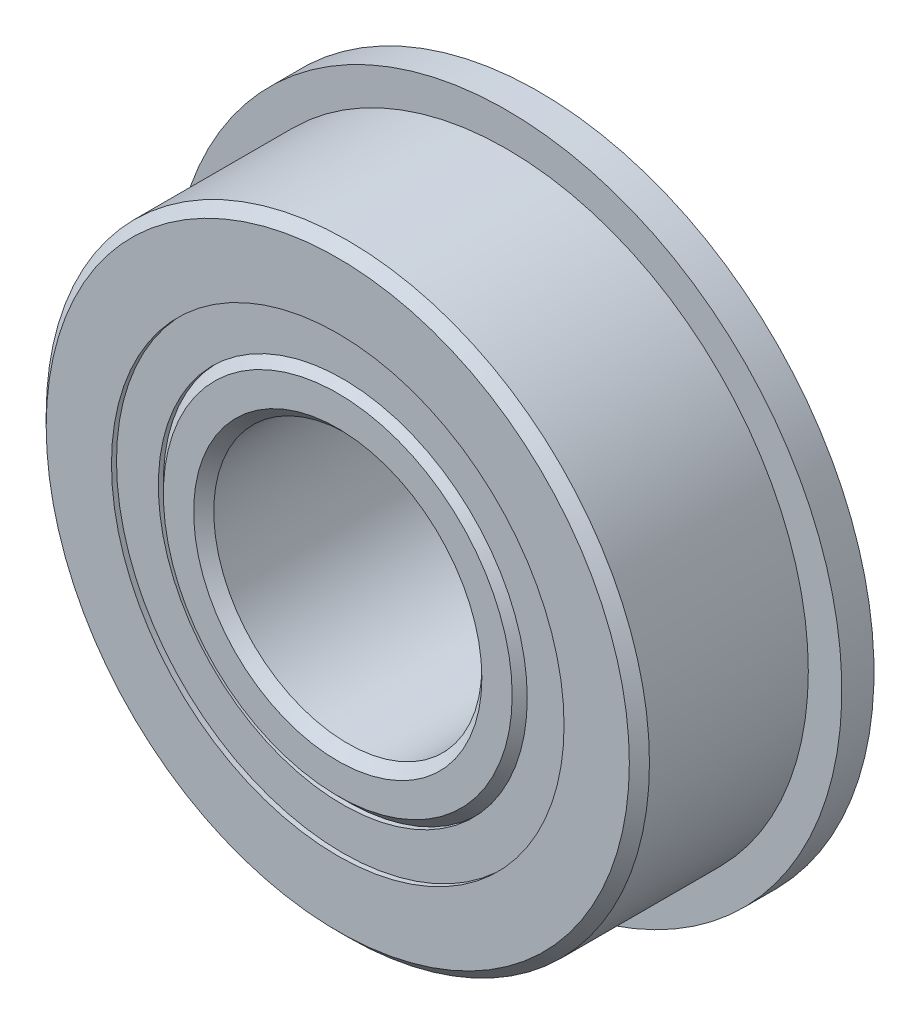
SolidWorks part; units mm, degrees
ref_plane "Front Plane" through (0, 0, 0) normal (0, 0, 1) x (1, 0, 0)
ref_plane "Top Plane" through (0, 0, 0) normal (0, 1, 0) x (1, 0, 0)
ref_plane "Right Plane" through (0, 0, 0) normal (1, 0, 0) x (0, 0, -1)
sketch "Sketch1" plane through (0, 0, 0) normal (1, 0, 0) x (0, 0, -1)
  line L0 (-4.7625, 0) -> (4.7625, 0) construction
  line L1 (0, 14.2875) -> (0, -14.2875) construction
  line L2 (4.2863, 14.2875) -> (-4.2862, 14.2875)
  line L3 (-4.2862, 14.2875) -> (-4.7625, 13.8112)
  line L4 (-4.7625, 13.8112) -> (-4.7625, 10.7188)
  line L5 (-4.7625, 10.7188) -> (-2.3474, 10.7188)
  line L6 (4.7625, 10.7188) -> (2.3474, 10.7188)
  line L7 (4.7625, 13.8112) -> (4.7625, 10.7188)
  line L8 (4.2863, 14.2875) -> (4.7625, 13.8112)
  line L9 (0, 14.2875) -> (0, 10.3187) construction
  line L10 (0, 10.3187) -> (0, 6.35) construction
  line L11 (4.7625, 8.7376) -> (4.7625, -8.7376) construction
  line L12 (-4.7625, 6.35) -> (4.7625, 6.35) construction
  line L13 (0, 7.9375) -> (0, 6.35) construction
  line L14 (0, 12.7) -> (0, 14.2875) construction
  line L15 (4.7625, 8.7376) -> (0, 8.7376) construction
  circle A1 centre (0, 10.3187) radius 2.3813 construction
  arc A2 (-2.3474, 10.7188) -> (2.3474, 10.7188) centre (0, 10.3187) cw
  point P14 (0, 6.35)
  point P22 (0, 7.9375)
  point P23 (0, 12.7)
  dimension "D3" = 4.7625
  dimension "Width" = 9.525
  dimension "OD" = 28.575
  dimension "D1" = 45
  dimension "D2" = 0.4763
  dimension "D4" = 17.4752
  dimension "D5" = 3.9624
  dimension "D6" = 1.9812
revolve "Revolve1" add sketch "Sketch1" angle 360 about L0
sketch "Sketch3" plane through (0, 0, 0) normal (1, 0, 0) x (0, 0, -1)
  line L1 (-4.7625, 13.8112) -> (-4.7625, 10.7188) construction
  line L2 (-4.2862, 14.2875) -> (-4.7625, 13.8112) construction
  line L3 (-4.7625, 9.9187) -> (-4.7625, 6.8262) construction
  line L4 (-4.7625, 6.8262) -> (-4.7625, 8.2614)
  line L5 (-4.7625, 6.8262) -> (-4.2862, 6.35)
  line L6 (-4.2862, 6.35) -> (5.8865, 6.35)
  line L7 (-4.7625, 13.8112) -> (-4.7625, -13.8112) construction
  line L8 (5.8865, 6.35) -> (6.3627, 6.8262)
  line L9 (0, 0) -> (6.3627, 0) construction
  line L13 (4.2863, 14.2875) -> (4.7625, 13.8112) construction
  line L14 (-4.7625, 8.2614) -> (-4.2862, 8.7376)
  line L15 (-4.2862, 8.7376) -> (-1.7805, 8.7376)
  line L16 (1.7805, 8.7376) -> (5.8865, 8.7376)
  line L17 (5.8865, 8.7376) -> (6.3627, 8.2614)
  line L18 (6.3627, 8.2614) -> (6.3627, 6.8262)
  circle A0 centre (0, 10.3187) radius 2.3812 construction
  arc A1 (-1.7805, 8.7376) -> (1.7805, 8.7376) centre (0, 10.3187) ccw
  dimension "D1" = 45
  dimension "Ring Wd" = 11.1252
  dimension "Inner Ring OD" = 17.4752
revolve "Revolve3" add sketch "Sketch3" angle 360 about L0
sketch "Sketch6" plane through (0, 0, 0) normal (1, 0, 0) x (0, 0, -1)
  line L1 (4.7625, 10.7188) -> (3.2385, 10.7188)
  line L2 (4.7625, 10.7188) -> (4.7625, 15.875)
  line L3 (4.7625, 15.875) -> (3.2385, 15.875)
  line L4 (3.2385, 10.7188) -> (3.2385, 15.875)
  line L5 (4.7625, 0) -> (-4.7625, 0) construction
  dimension "Flange OD" = 31.75
  dimension "Flange Thickness" = 1.524
revolve "Revolve6" add sketch "Sketch6" angle 360 about L5
sketch "Sketch4" plane through (0, 0, 0) normal (1, 0, 0) x (0, 0, -1)
  line L0 (-2.3813, 10.3187) -> (2.3813, 10.3187)
  circle A0 centre (0, 10.3187) radius 2.3812 construction
  arc A1 (2.3813, 10.3187) -> (-2.3813, 10.3187) centre (0, 10.3187) ccw
revolve "Revolve4" add sketch "Sketch4" angle 360 about L0
ref_axis "Axis1" through (0, 0, -4.7625) along (0, 0, 1)
pattern_circular "CirPattern1" count 12 every 30 about axis through (0, 0, -4.7625) along (0, 0, 1) of bodies 104
sketch "Sketch5" plane through (0, 0, 0) normal (1, 0, 0) x (0, 0, -1)
  line L0 (-4.7625, 10.7188) -> (-2.3474, 10.7188) construction
  line L1 (-4.5244, 10.7188) -> (-1.7805, 10.7188)
  line L2 (-4.5244, 10.7188) -> (-4.5244, 8.7376)
  line L3 (-4.5244, 8.7376) -> (-1.7805, 8.7376)
  line L4 (-1.7805, 10.7188) -> (-1.7805, 8.7376)
  line L6 (4.7625, 10.7188) -> (2.3474, 10.7188) construction
  line L7 (4.5244, 10.7188) -> (1.7805, 10.7188)
  line L8 (4.5244, 10.7188) -> (4.5244, 8.7376)
  line L9 (4.5244, 8.7376) -> (1.7805, 8.7376)
  line L10 (1.7805, 10.7188) -> (1.7805, 8.7376)
  line L12 (-4.2862, 14.2875) -> (-4.7625, 13.8112) construction
  line L13 (4.7625, 8.7376) -> (0, 8.7376) construction
  line L15 (-4.2862, 8.7376) -> (-1.7805, 8.7376) construction
  line L16 (4.5244, 10.7188) -> (4.5244, 14.0494) construction
  line L17 (4.2863, 14.2875) -> (4.7625, 13.8112) construction
  point P18 (-4.5244, 14.0494)
revolve "Revolve5" add sketch "Sketch5" angle 360 about L0
equation "\"D2@Sketch1\" = \"Width@Sketch1\"*.05"
equation "\"D2@CirPattern1\" = 360/\"Balls@CirPattern1\""
equation "\"D4@Sketch1\"=\"Inner Ring OD@Sketch3\""
equation "\"D3@Sketch1\"=\"Width@Sketch1\"/2"
equation "\"D6@Sketch1\"=\"D5@Sketch1\"/2"
